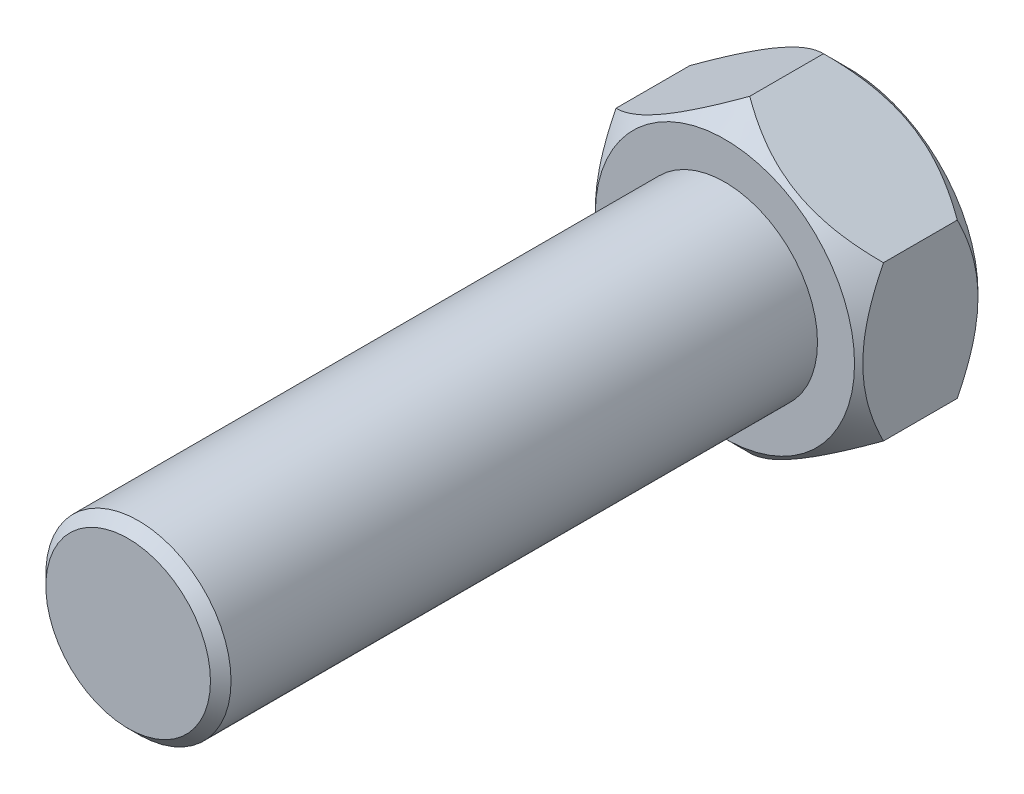
SolidWorks part; units mm, degrees
material "Alloy Steel"
ref_plane "Front Plane" through (0, 0, 0) normal (0, 0, 1) x (1, 0, 0)
ref_plane "Top Plane" through (0, 0, 0) normal (0, 1, 0) x (1, 0, 0)
ref_plane "Right Plane" through (0, 0, 0) normal (1, 0, 0) x (0, 0, -1)
sketch "Sketch1" plane through (0, 0, 0) normal (0, 0, 1) x (1, 0, 0)
  line L1 (0, -9.5321) -> (8.255, -4.766)
  line L2 (8.255, -4.766) -> (8.255, 4.766)
  line L3 (8.255, 4.766) -> (0, 9.5321)
  line L4 (0, 9.5321) -> (-8.255, 4.766)
  line L5 (-8.255, 4.766) -> (-8.255, -4.766)
  line L6 (-8.255, -4.766) -> (0, -9.5321)
  circle A0 centre (0, 0) radius 5.715
  circle A1 centre (0, 0) radius 8.255 construction
  dimension "D1" = 11.43
  dimension "D2" = 2.54
extrude "Boss-Extrude1" add sketch "Sketch1" along normal blind 36.83 contours A0 region at (0, 0, 0)
extrude "Boss-Extrude2" add sketch "Sketch1<3>" against normal blind 7.62 contours A0 | L5 L6 L1 L2 L3 L4 A0 region at (-4.0014, -6.9306, 0) region at (0, 0, 0)
sketch "Sketch1<3>" plane through (0, 0, 0) normal (0, 0, 1) x (1, 0, 0) same geometry as "Sketch1"
sketch "Sketch2" plane through (0, 0, 0) normal (0, 1, 0) x (1, 0, 0)
  line L0 (8.001, 0) -> (11.811, 3.81)
  line L1 (8.255, 0) -> (0, 0) construction
  line L2 (11.811, 3.81) -> (8.001, 7.62)
  line L3 (8.255, 7.62) -> (0, 7.62) construction
  line L4 (8.001, 0) -> (14.351, 0)
  line L5 (14.351, 0) -> (14.351, 7.62)
  line L6 (14.351, 7.62) -> (8.001, 7.62)
  line L7 (8.255, 7.62) -> (8.255, 0) construction
  line L8 (0, 0) -> (0, 3.1529) construction
  dimension "D1" = 45
  dimension "D2" = 2.54
  dimension "D3" = 0.254
revolve "Cut-Revolve1" cut sketch "Sketch2" angle 360 about L8
chamfer "Chamfer1" distance 0.635 angle 45 1 edges at (5.715, 0, 36.83)
